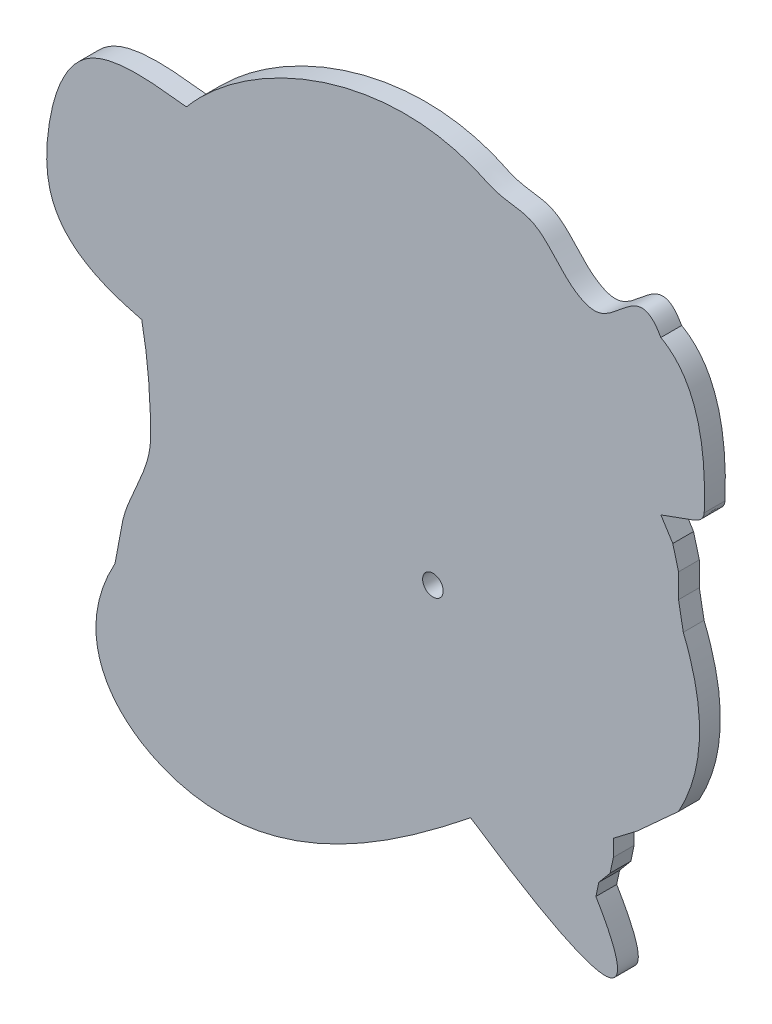
SolidWorks part; units mm, degrees
ref_plane "Front Plane" through (0, 0, 0) normal (0, 0, 1) x (1, 0, 0)
ref_plane "Top Plane" through (0, 0, 0) normal (0, 1, 0) x (1, 0, 0)
ref_plane "Right Plane" through (0, 0, 0) normal (1, 0, 0) x (0, 0, -1)
sketch "Sketch1" plane through (0, 0, 0) normal (0, 0, 1) x (1, 0, 0)
  line L0 (134.6667, 500.5) -> (673.3333, 500.5) construction
  line L9 (158.8486, 158.066) -> (159.2873, 160.158)
  line L10 (159.2873, 160.158) -> (161.0243, 162.2425)
  line L11 (161.0243, 162.2425) -> (161.5128, 164.5724)
  line L12 (161.5128, 164.5724) -> (161.5128, 167.1023)
  line L13 (161.5128, 167.1023) -> (165.1835, 169.9013)
  line L14 (165.1835, 169.9013) -> (171.472, 175.6217)
  line L15 (86.5908, 171.7678) -> (85.3882, 165.3811)
  line L16 (168.7713, 213.5075) -> (170.5915, 210.6336)
  line L17 (170.5915, 210.6336) -> (171.472, 207.3286)
  line L18 (171.472, 207.3286) -> (171.472, 203.6405)
  line L19 (171.472, 203.6405) -> (172.1964, 199.6877)
  line L21 (168.7713, 213.5075) -> (173.7621, 215.3232)
  circle A0 centre (133.9499, 186.811) radius 1.5748
  spline S0 degree 3 poles (85.3882, 165.3811) (78.0487, 152.0358) (100.0626, 129.8424) (127.3192, 149.0039) (139.7108, 158.9096) knots 0 0 0 0 0.355984 1 1 1 1
  spline S1 degree 2 poles (139.7108, 158.9096) (170.7543, 138.1113) (158.8486, 158.066) knots 0 0 0 1 1 1
  spline S2 degree 3 poles (89.473, 199.6877) (76.4141, 202.7784) (72.921, 212.6954) (79.1309, 233.8673) (92.3571, 231.6545) (96.3054, 231.2529) knots 0 0 0 0 0.435393 0.719887 1 1 1 1
  spline S3 degree 2 poles (168.7713, 236.9728) (176.0245, 232.9136) (175.3973, 217.0895) knots 0 0 0 1 1 1
  spline S4 degree 2 poles (173.7621, 215.3232) (175.2991, 215.89) (175.3973, 217.0895) knots 0 0 0 1 1 1
  spline S5 degree 3 poles (168.7713, 236.9728) (165.3483, 243.1818) (161.713, 233.5905) (153.5919, 237.311) (150.5622, 243.2925) (144.2663, 243.1727) (127.5396, 251.7095) (106.0894, 242.9451) (96.3054, 231.2529) knots 0 0 0 0 0.145953 0.187032 0.301265 0.367852 0.402075 1 1 1 1
  spline S11 degree 2 poles (172.1964, 199.6877) (177.5125, 186.6119) (171.472, 175.6217) knots 0 0 0 1 1 1
  spline S12 degree 3 poles (89.473, 199.6877) (90.4497, 194.8375) (90.826, 189.8378) (90.8383, 180.2807) (87.6783, 176.1914) (86.5908, 171.7678) knots 0 0 0 0 0.517811 0.520823 1 1 1 1
extrude "Boss-Extrude2" add sketch "Sketch1" along normal blind 3.175
